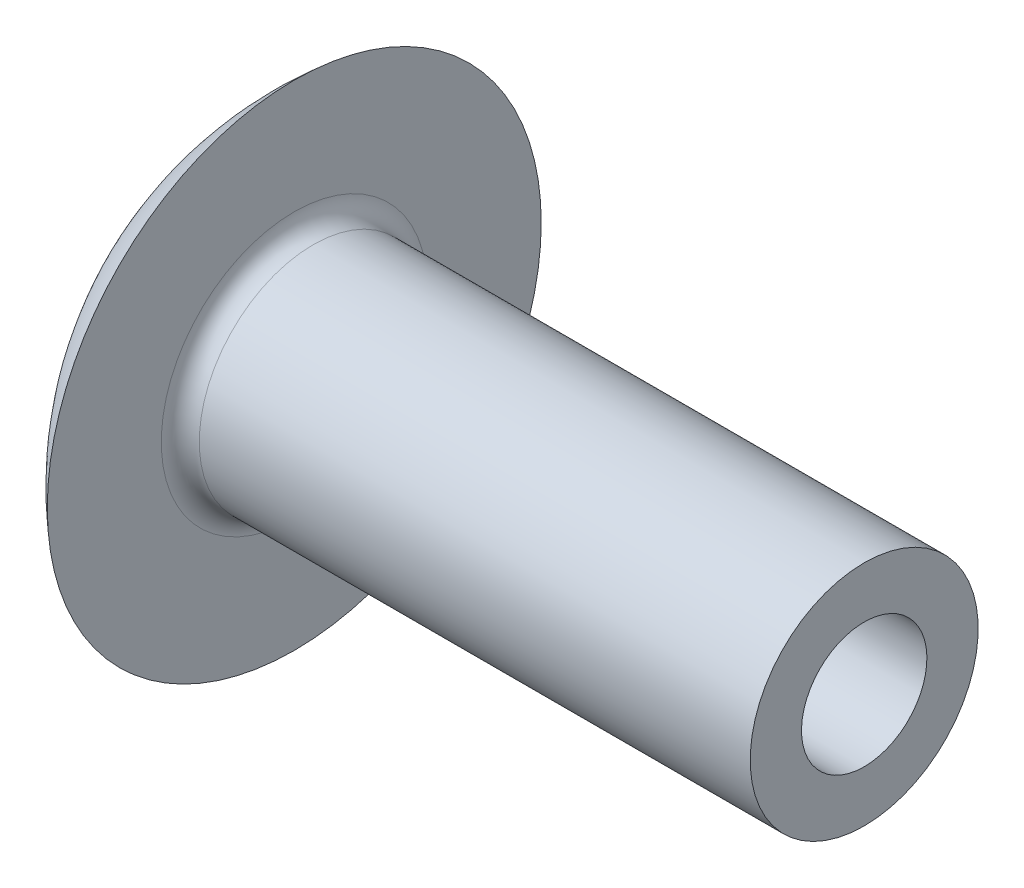
SolidWorks part; units mm, degrees
ref_plane "Front" through (0, 0, 0) normal (0, 0, 1) x (1, 0, 0)
ref_plane "Top" through (0, 0, 0) normal (0, 1, 0) x (1, 0, 0)
ref_plane "Right" through (0, 0, 0) normal (1, 0, 0) x (0, 0, -1)
sketch "Sketch1" plane through (4.2423, 2.9423, 0) normal (0, 0, 1) x (0, 1, 0)
  line L0 (-2.6123, 0.6423) -> (-2.3423, 0.6423)
  line L1 (-2.3423, 0.6423) -> (-2.3423, 3.6423)
  line L2 (-2.3423, 3.6423) -> (-1.6423, 3.6423)
  line L3 (-2.9423, 11.1005) -> (-2.9423, -2.6313) construction
  line L4 (-2.9423, 2.2728) -> (-2.9423, 4.2423)
  line L5 (-2.6123, 0.6423) -> (-2.6123, 2.0823)
  line L6 (-2.6123, 2.0823) -> (-2.9423, 2.2728)
  arc A0 (-1.6423, 3.6423) -> (-2.9423, 4.2423) centre (-2.9423, 2.534) ccw
  dimension "l" = 3
  dimension "d" = 1.2
  dimension "D2" = 60
  dimension "dk" = 2.6
  dimension "K" = 0.6
  dimension "dt" = 0.66
  dimension "t" = 1.44
revolve "Base-Revolve" add sketch "Sketch1" angle 360 about L3
fillet "Fillet1" radius 0.1 1 edges at (0.6, -0.6, 0)
